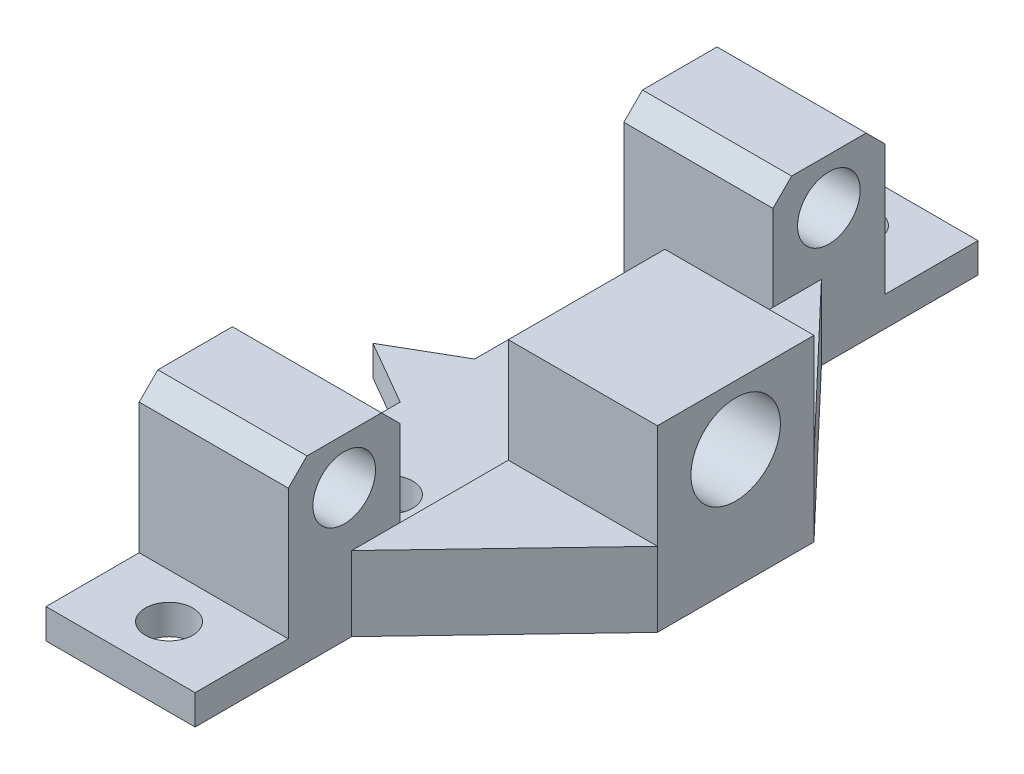
SolidWorks part; units mm, degrees
ref_plane "Front Plane" through (0, 0, 0) normal (0, 0, 1) x (1, 0, 0)
ref_plane "Top Plane" through (0, 0, 0) normal (0, 1, 0) x (1, 0, 0)
ref_plane "Right Plane" through (0, 0, 0) normal (1, 0, 0) x (0, 0, -1)
sketch "Sketch1" plane through (0, 0, 0) normal (0, 1, 0) x (1, 0, 0)
  line L1 (0, 0) -> (20, 0)
  line L2 (0, 0) -> (0, 105)
  line L3 (0, 105) -> (20, 105)
  line L4 (20, 0) -> (20, 105)
  dimension "D1" = 105
  dimension "D2" = 20
extrude "Boss-Extrude1" add sketch "Sketch1" along normal blind 4
sketch "Sketch2" plane through (0, 0, 0) normal (-1, 0, 0) x (0, 0, 1)
  line L0 (-105, 0) -> (0, 0) construction
  line L5 (-12.5, 21.5) -> (-15, 24)
  line L6 (-92.5, 0) -> (-77.5, 0)
  line L7 (-92.5, 0) -> (-92.5, 24)
  line L8 (-92.5, 24) -> (-77.5, 24)
  line L9 (-77.5, 0) -> (-77.5, 24)
  line L10 (-105, 0) -> (-92.5, 0) construction
  line L11 (-80, 24) -> (-77.5, 21.5)
  line L12 (-92.5, 21.5) -> (-90, 24)
  line L13 (-52.5, 0) -> (-52.5, 4) construction
  line L14 (-25, 24) -> (-27.5, 21.5)
  line L15 (-105, 4) -> (0, 4) construction
  line L16 (-27.5, 0) -> (-27.5, 24)
  line L17 (-12.5, 24) -> (-27.5, 24)
  line L18 (-12.5, 0) -> (-12.5, 24)
  line L19 (-12.5, 0) -> (-27.5, 0)
  circle A0 centre (-85, 17.8) radius 4.2
  circle A1 centre (-20, 17.8) radius 4.2
  point P10 (-85, 24)
  point P25 (-52.5, 4)
  point P30 (-20, 24)
  line M15 (0, 4) -> (-105, 4)
  dimension "D4" = 8.4
  dimension "D2" = 15
  dimension "D3" = 24
  dimension "D6" = 2.5
  dimension "D7" = 2.5
  dimension "D8" = 2.5
  dimension "D9" = 2.5
  dimension "D1" = 65
  dimension "D5" = 6.2
extrude "Boss-Extrude2" add sketch "Sketch2" against normal up to surface (20 mm away) contours L18 L5 L17 L14 L16 A1 M15 | L12 L7 L9 L11 L8 A0 M15 region at (0, 12.876, -20) region at (0, 12.876, -85) up to face at (20, 2, -52.5)
sketch "Sketch3" plane through (0, 0, 0) normal (0, -1, 0) x (1, 0, 0)
  line L0 (0, -57.5) -> (-8.6603, -52.5)
  line L1 (0, -105) -> (0, 0) construction
  line L2 (-8.6603, -52.5) -> (0, -47.5)
  line L3 (0, -57.5) -> (0, -47.5)
  point P6 (0, -52.5)
  dimension "D1" = 10
  dimension "D2" = 10
  dimension "D3" = 10
extrude "Boss-Extrude3" add sketch "Sketch3" against normal up to surface (4 mm away) up to face at (10, 4, -98.75)
sketch "Sketch4" plane through (0, 4, 0) normal (0, 1, 0) x (1, 0, 0)
  line L0 (10, 105) -> (10, 0) construction
  line L1 (20, 105) -> (0, 105) construction
  line L2 (0, 0) -> (20, 0) construction
  circle A0 centre (10, 98.5) radius 3.175
  circle A1 centre (10, 69) radius 3.175
  circle A2 centre (10, 36) radius 3.175
  circle A3 centre (10, 6.5) radius 3.175
  dimension "D1" = 6.35
  dimension "D2" = 6.5
  dimension "D3" = 36
  dimension "D4" = 6.5
  dimension "D5" = 36
extrude "Cut-Extrude1" cut sketch "Sketch4" against normal through all
sketch "Sketch5" plane through (20, 0, 0) normal (1, 0, 0) x (0, 0, -1)
  line L0 (0, 0) -> (105, 0) construction
  line L1 (42, 0) -> (63, 0)
  line L2 (42, 0) -> (42, 24)
  line L3 (42, 24) -> (63, 24)
  line L4 (63, 0) -> (63, 24)
  line L5 (63, 0) -> (105, 0) construction
  line L10 (25, 24) -> (15, 24) construction
  line L12 (42, 0) -> (0, 0) construction
  dimension "D1" = 21
extrude "Boss-Extrude4" add sketch "Sketch5" along normal blind 20
sketch "Sketch6" plane through (40, 0, 0) normal (1, 0, 0) x (0, 0, -1)
  line L0 (52.5, 24) -> (52.5, 0) construction
  line L1 (63, 24) -> (42, 24) construction
  line L2 (42, 0) -> (63, 0) construction
  circle A0 centre (52.5, 16) radius 6
  dimension "D1" = 12
  dimension "D2" = 8
extrude "Cut-Extrude2" cut sketch "Sketch6" against normal through all
sketch "Sketch11" plane through (0, 0, 0) normal (0, -1, 0) x (1, 0, 0)
  line L0 (40, -63) -> (20, -84)
  line L1 (20, -63) -> (20, -105) construction
  line L2 (40, -63) -> (20, -63)
  line L3 (20, -63) -> (20, -84)
  line L4 (40, -42) -> (20, -42)
  line L5 (20, -42) -> (20, -21)
  line L7 (20, -21) -> (40, -42)
  line L8 (20, 0) -> (20, -42) construction
extrude "Boss-Extrude5" add sketch "Sketch11" against normal blind 10
equation "\"8mm hole\" = 8.4mm"
equation "\"D4@Sketch2\"= \"8mm hole\""
equation "\"22mm hole\"= 23mm"
equation "\"15mm hole\"= 15.8mm"
equation "\"bed height offset\"= 3mm"
equation "\"D3@Sketch2\"= 21 + \"bed height offset\""
